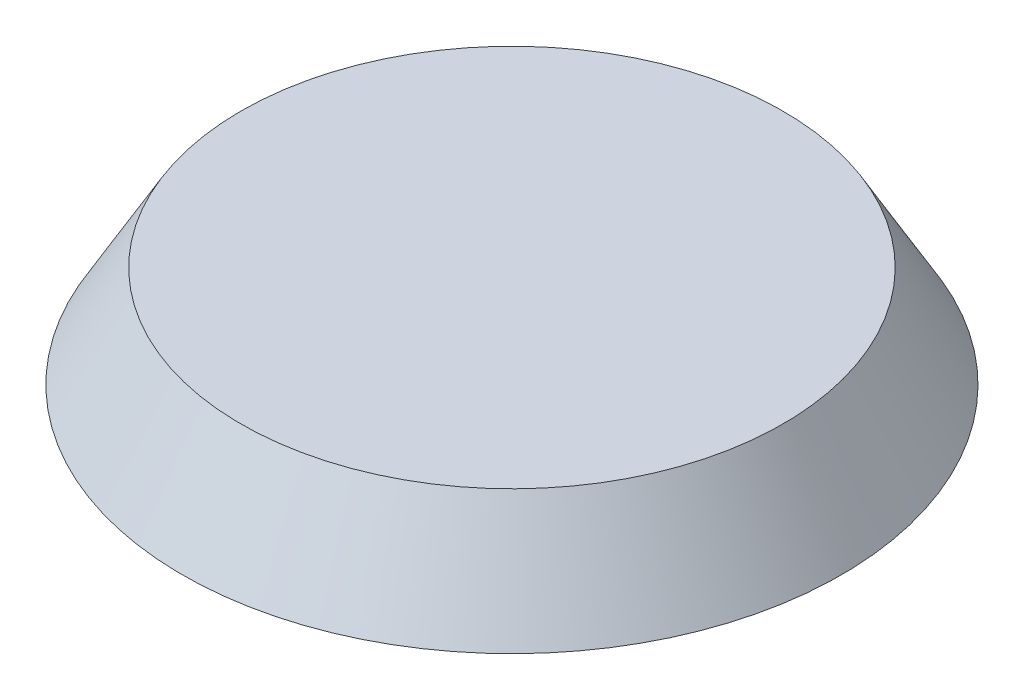
SolidWorks part; units mm, degrees
ref_plane "Front Plane" through (0, 0, 0) normal (0, 0, 1) x (1, 0, 0)
ref_plane "Top Plane" through (0, 0, 0) normal (0, 1, 0) x (1, 0, 0)
ref_plane "Right Plane" through (0, 0, 0) normal (1, 0, 0) x (0, 0, -1)
sketch "Sketch2" plane through (0, 0, 0) normal (0, 1, 0) x (1, 0, 0)
  circle A0 centre (0, 0) radius 54.4425
  dimension "D1" = 108.885
extrude "Boss-Extrude1" add sketch "Sketch2" along normal blind 5
sketch "Sketch4" plane through (0, 0, 0) normal (0, 0, 1) x (1, 0, 0)
  line L0 (0, 5) -> (65, 5)
  line L1 (65, 5) -> (53.453, 25)
  line L2 (53.453, 25) -> (0, 25)
  line L3 (0, 25) -> (0, 5)
  point P2 (0, 0)
  point P7 (0, 5.1623)
  dimension "D1" = 65
  dimension "D2" = 60
  dimension "D3" = 20
revolve "Revolve1" add sketch "Sketch4" angle 360 about L3
